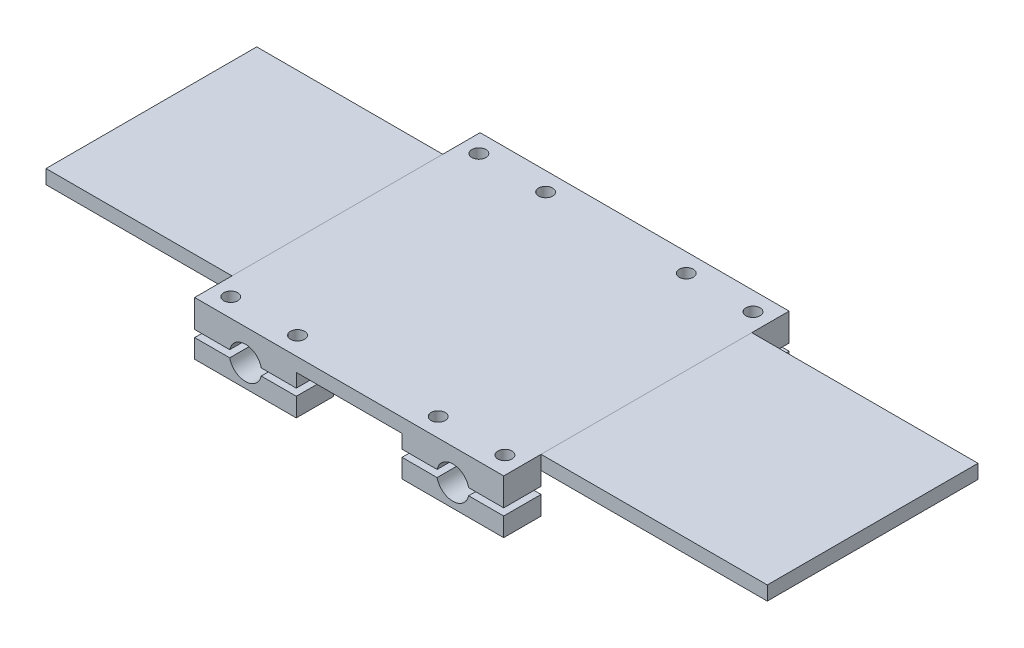
SolidWorks part; units mm, degrees
ref_plane "Front Plane" through (0, 0, 0) normal (0, 0, 1) x (1, 0, 0)
ref_plane "Top Plane" through (0, 0, 0) normal (0, 1, 0) x (1, 0, 0)
ref_plane "Right Plane" through (0, 0, 0) normal (1, 0, 0) x (0, 0, -1)
sketch "Sketch1" plane through (0, 0, 0) normal (0, 0, 1) x (1, 0, 0)
  line L0 (73.8188, 0) -> (0, 0) construction
  line L1 (-110, -15.875) -> (110, -15.875)
  line L2 (-110, -15.875) -> (-110, 15.875)
  line L3 (-110, 15.875) -> (110, 15.875)
  line L4 (110, -15.875) -> (110, 15.875)
  line L5 (-110, -15.875) -> (110, 15.875) construction
  line L6 (-110, 15.875) -> (110, -15.875) construction
  line L7 (0, 0) -> (-73.8187, 0) construction
  circle A1 centre (-73.8187, 0) radius 11.5
  circle A2 centre (73.8188, 0) radius 11.5
  point P0 (0, 0)
  dimension "D1" = 147.6375
  dimension "D4" = 23
  dimension "D2" = 31.75
  dimension "D3" = 220
extrude "Boss-Extrude1" add sketch "Sketch1" along normal blind 203.2
sketch "Sketch3" plane through (0, 0, 203.2) normal (0, 0, 1) x (1, 0, 0)
  line L0 (110, -15.875) -> (110, 15.875) construction
  line L1 (-110, 15.875) -> (110, 15.875)
  line L2 (-110, 15.875) -> (-110, 22.225)
  line L3 (-110, 22.225) -> (110, 22.225)
  line L4 (110, 15.875) -> (110, 22.225)
  dimension "D1" = 6.35
extrude "Boss-Extrude2" add sketch "Sketch3" against normal up to surface (203.2 mm away) up to face at (-62.3188, 0, 0)
sketch "Sketch4" plane through (-110, 0, 0) normal (-1, 0, 0) x (0, 0, 1)
  line L0 (203.2, -15.875) -> (0, -15.875) construction
  line L1 (26.6, -15.875) -> (176.6, -15.875)
  line L2 (26.6, -15.875) -> (26.6, 12.225)
  line L3 (26.6, 12.225) -> (176.6, 12.225)
  line L4 (176.6, -15.875) -> (176.6, 12.225)
  line L5 (0, 0) -> (26.6, 0) construction
  line L6 (26.6, 0) -> (176.6, 0) construction
  line L7 (176.6, 0) -> (203.2, 0) construction
  line L8 (203.2, 22.225) -> (203.2, -15.875) construction
  line L9 (0, 22.225) -> (203.2, 22.225) construction
  dimension "D1" = 10
  dimension "D2" = 150
extrude "Cut-Extrude1" cut sketch "Sketch4" against normal blind 253.2
sketch "Sketch5" plane through (0, 0, 0) normal (0, 0, -1) x (-1, 0, 0)
  line L0 (110, -15.875) -> (-110, -15.875) construction
  line L1 (-37.6375, -15.875) -> (37.6375, -15.875)
  line L2 (-37.6375, -15.875) -> (-37.6375, 12.225)
  line L3 (-37.6375, 12.225) -> (37.6375, 12.225)
  line L4 (37.6375, -15.875) -> (37.6375, 12.225)
  line L5 (-110, 22.225) -> (110, 22.225) construction
  line L6 (0, 0) -> (-37.6375, 0) construction
  line L7 (0, 0) -> (37.6375, 0) construction
  line L8 (-37.6375, 0) -> (-73.8188, 0) construction
  line L9 (-73.8188, 0) -> (-110, 0) construction
  line L10 (-110, -15.875) -> (-110, 22.225) construction
  dimension "D1" = 10
extrude "Cut-Extrude2" cut sketch "Sketch5" against normal blind 203.2
sketch "Sketch6" plane through (0, -15.875, 0) normal (0, -1, 0) x (1, 0, 0)
  line L0 (-110, 189.9) -> (-97.5688, 189.9) construction
  line L2 (-97.5688, 189.9) -> (-50.0688, 189.9) construction
  line L3 (-50.0688, 189.9) -> (-37.6375, 189.9) construction
  line L5 (-110, 13.3) -> (-97.5688, 13.3) construction
  line L6 (-110, 26.6) -> (-110, 0) construction
  line L7 (-97.5688, 13.3) -> (-50.0688, 13.3) construction
  line L8 (-50.0688, 13.3) -> (-37.6375, 13.3) construction
  line L9 (-37.6375, 26.6) -> (-37.6375, 0) construction
  line L10 (37.6375, 203.2) -> (37.6375, 176.6) construction
  line L11 (37.6375, 26.6) -> (37.6375, 0) construction
  line L12 (37.6375, 13.3) -> (50.0688, 13.3) construction
  line L13 (50.0688, 13.3) -> (97.5687, 13.3) construction
  line L14 (97.5687, 13.3) -> (110, 13.3) construction
  line L16 (-62.3188, 203.2) -> (-85.3187, 203.2) construction
  line L18 (110, 189.9) -> (97.5687, 189.9) construction
  line L19 (97.5687, 189.9) -> (50.0688, 189.9) construction
  line L20 (50.0688, 189.9) -> (37.6375, 189.9) construction
  line L22 (-62.3188, 203.2) -> (-85.3187, 203.2)
  line L23 (-85.3187, 203.2) -> (-85.3187, 0) construction
  line L24 (-110, 0) -> (-37.6375, 0) construction
  line L25 (-62.3188, 203.2) -> (-62.3188, 0) construction
  line L28 (-37.6375, 203.2) -> (-37.6375, 176.6) construction
  line L29 (-110, 203.2) -> (-110, 176.6) construction
  line L30 (110, 203.2) -> (110, 176.6) construction
  circle A0 centre (-50.0688, 189.9) radius 5
  circle A1 centre (-97.5688, 189.9) radius 5
  circle A2 centre (-97.5688, 13.3) radius 5
  circle A3 centre (-50.0688, 13.3) radius 5
  circle A4 centre (50.0688, 13.3) radius 5
  circle A5 centre (97.5687, 13.3) radius 5
  circle A6 centre (97.5687, 189.9) radius 5
  circle A7 centre (50.0688, 189.9) radius 5
  point P2 (-100, 189.9)
  point P3 (-47.6375, 189.9)
  point P7 (37.6375, 189.9)
  point P24 (-110, 190.63)
  point P26 (-37.6375, 189.9)
  point P32 (-110, 189.9)
  point P47 (0, 0)
  point P48 (0, 0)
  point P49 (0, 0)
  point P50 (-102.2029, 189.9)
  point P53 (103.4074, 13.3)
  point P56 (92.8187, 189.9)
  dimension "D1" = 10
  dimension "D2" = 47.5
extrude "Cut-Extrude3" cut sketch "Sketch6" against normal blind 203.2 contours A4 | A5 | A3 | A2 | A1 | A0 | A7 | A6
sketch "Sketch7" plane through (0, 0, 0) normal (0, 0, -1) x (-1, 0, 0)
  line L0 (-110, -15.875) -> (-110, 22.225) construction
  line L1 (110, -2.5) -> (-110, -2.5)
  line L2 (110, -2.5) -> (110, 2.5)
  line L3 (110, 2.5) -> (-110, 2.5)
  line L4 (-110, -2.5) -> (-110, 2.5)
  line L5 (110, -2.5) -> (-110, 2.5) construction
  line L6 (110, 2.5) -> (-110, -2.5) construction
  point P0 (0, 0)
  dimension "D1" = 5
extrude "Cut-Extrude4" cut sketch "Sketch7" against normal blind 203.2
sketch "Sketch8" plane through (-110, 0, 0) normal (-1, 0, 0) x (0, 0, 1)
  line L0 (176.6, 12.225) -> (26.6, 12.225) construction
  line L1 (176.6, 12.225) -> (26.6, 12.225)
  line L2 (176.6, 12.225) -> (176.6, 22.225)
  line L3 (176.6, 22.225) -> (26.6, 22.225)
  line L4 (26.6, 12.225) -> (26.6, 22.225)
  line L5 (0, 22.225) -> (203.2, 22.225) construction
  point P8 (26.6, 12.225)
  point P9 (176.6, 12.225)
  point P10 (157.0914, 11.0484)
  point P12 (42.9616, 12.225)
  line M4 (26.6, 12.225) -> (176.6, 12.225)
  line M8 (203.2, 22.225) -> (0, 22.225)
extrude "Boss-Extrude3" add sketch "Sketch8" along normal blind 132.4137 contours L4 L2 M4 M8 region at (-110, 17.225, 101.6)
sketch "Sketch9" plane through (110, 0, 0) normal (1, 0, 0) x (0, 0, -1)
  line L0 (-176.6, 12.225) -> (-26.6, 12.225) construction
  line L1 (-176.6, 12.225) -> (-26.6, 12.225)
  line L2 (-176.6, 12.225) -> (-176.6, 22.225)
  line L3 (-176.6, 22.225) -> (-26.6, 22.225)
  line L4 (-26.6, 12.225) -> (-26.6, 22.225)
  line L5 (0, 22.225) -> (-203.2, 22.225) construction
  point P8 (-168.6153, 12.225)
  point P9 (-33.5794, 12.225)
  point P10 (0, 0)
  point P11 (0, 0)
extrude "Boss-Extrude4" add sketch "Sketch9" along normal blind 161.0473
ref_plane "Plane1" through (-110, 0, 0) normal (-1, 0, 0) x (0, 0, 1)
ref_plane "Plane2" through (110, 0, 0) normal (1, 0, 0) x (0, 0, -1)
split line "Split Line1"
split line "Split Line2"
